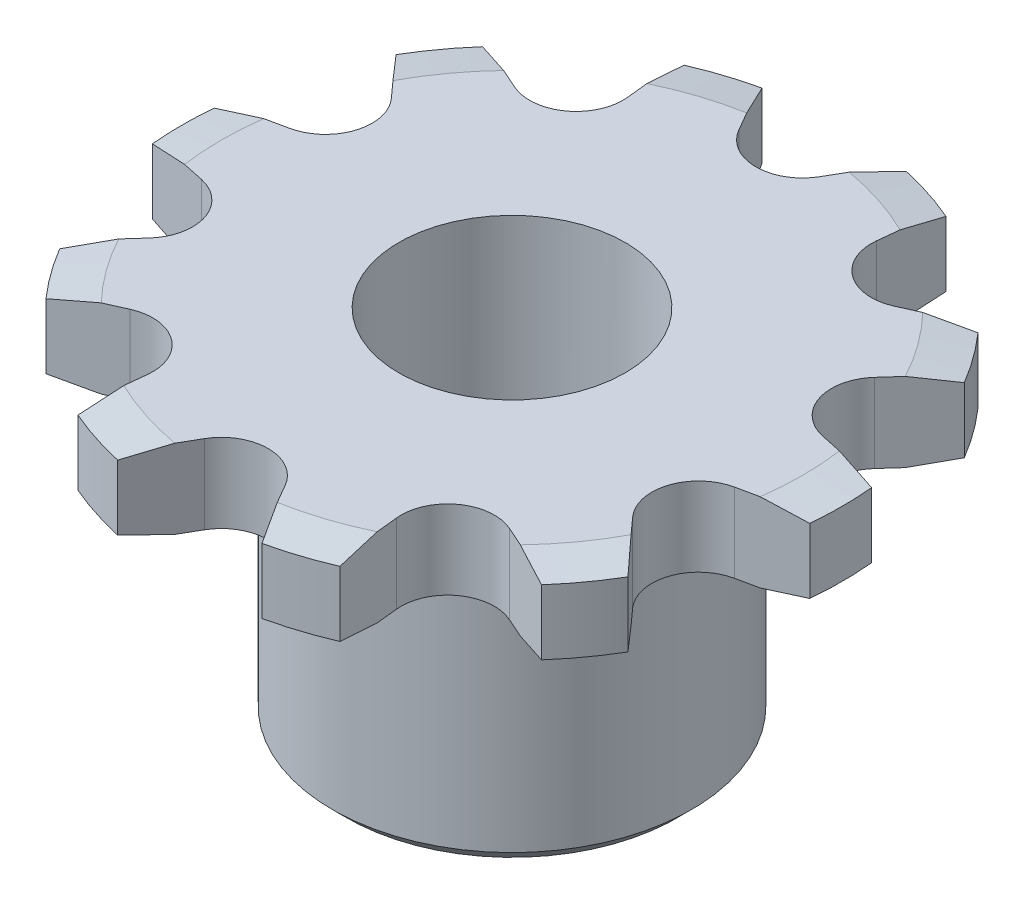
SolidWorks part; units mm, degrees
material "S45C"
ref_plane "Front" through (0, 0, 0) normal (0, 0, 1) x (1, 0, 0)
ref_plane "Top" through (0, 0, 0) normal (0, 1, 0) x (1, 0, 0)
ref_plane "Right" through (0, 0, 0) normal (1, 0, 0) x (0, 0, -1)
ref_axis "X" through (-3.9181, 0, 0) along (1, 0, 0)
ref_axis "Y" through (0, 3.9181, 0) along (0, -1, 0)
ref_axis "Z" through (0, 0, -0.05) along (0, 0, 1)
sketch "Sketch1" plane through (0, 0, 0) normal (0, 0, 1) x (1, 0, 0)
  line L0 (0, 0) -> (0, -12.7) construction
  line L1 (0, 0) -> (10.2745, 0)
  line L2 (11.6766, -0.2472) -> (11.6766, -2.5468)
  line L3 (10.2745, -2.794) -> (6.35, -2.794)
  line L4 (6.35, -2.794) -> (6.35, -12.2)
  line L5 (5.85, -12.7) -> (0, -12.7)
  line L6 (10.2745, 0) -> (11.6766, -0.2472)
  line L7 (10.2745, -2.794) -> (11.6766, -2.5468)
  line L8 (0, 0) -> (0, -12.7)
  line L9 (6.35, -12.2) -> (5.85, -12.7)
  point P7 (6.35, -12.7)
  dimension "OD" = 23.3533
  dimension "HD" = 12.7
  dimension "L" = 12.7
  dimension "D4" = 2.794
  dimension "D5" = 10
  dimension "D6" = 10
  dimension "PCD" = 20.549
revolve "Revolve2" add sketch "Sketch1" angle 360 about L0
sketch "Sketch2" plane through (0, 0, 0) normal (0, 1, 0) x (1, 0, 0)
  line L0 (0, 0) -> (0, 11.6766) construction
  line L1 (1.4289, 9.4495) -> (2.5518, 11.3944)
  line L2 (-1.4289, 9.4495) -> (-2.5518, 11.3944)
  circle A0 centre (0, 0) radius 11.6766 construction
  circle A1 centre (0, 0) radius 10.2745 construction
  arc A2 (-1.4289, 9.4495) -> (1.4289, 9.4495) centre (0, 10.2745) ccw
  arc A3 (2.5518, 11.3944) -> (-2.5518, 11.3944) centre (0, 0) ccw
  circle A4 centre (0, 0) radius 10.2745 construction
  dimension "D2" = 3.3
  dimension "D3" = 30
extrude "Cut-Extrude1" cut sketch "Sketch2" against normal up to surface (2.794 mm away) up to face at (-10.2745, -2.794, 0)
pattern_circular "CirPattern1" count 10 every 36 about axis through (0, 0, 0) along (0, 1, 0) of "Cut-Extrude1"
other "PropertyManager"
sketch "Sketch3" plane through (0, -12.7, 0) normal (0, -1, 0) x (1, 0, 0)
  circle A0 centre (0, 0) radius 4
extrude "Cut-Extrude2" cut sketch "Sketch3" against normal through all
sketch "Sketch4" plane through (0, 0, 0) normal (1, 0, 0) x (0, 0, -1)
  line L0 (0, -12.7) -> (0, -2.794) construction
  line L1 (-5.85, -12.7) -> (5.85, -12.7) construction
  line L2 (-1.4017, -2.794) -> (1.4017, -2.794) construction
  circle A0 centre (0, -7.747) radius 2.25
extrude "Cut-Extrude3" cut sketch "Sketch4" against normal blind 10
sketch "Sketch5" plane through (0, 0, 0) normal (0, 0, 1) x (1, 0, 0)
  line L0 (0, -2.794) -> (0, -12.2) construction
  line L1 (-1.4289, -2.794) -> (1.4289, -2.794) construction
  line L2 (-6.35, -12.2) -> (6.35, -12.2) construction
  circle A0 centre (0, -7.497) radius 2.25
extrude "Cut-Extrude4" cut sketch "Sketch5" against normal blind 10
